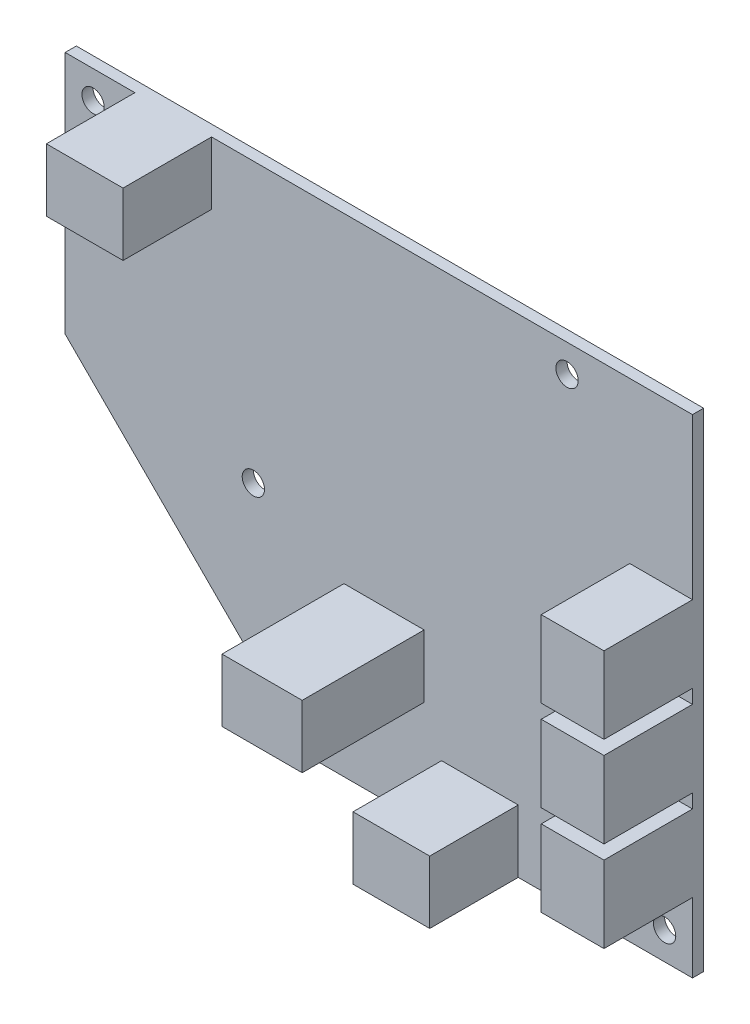
SolidWorks part; units mm, degrees
ref_plane "Plan de face" through (0, 0, 0) normal (0, 0, 1) x (1, 0, 0)
ref_plane "Plan de dessus" through (0, 0, 0) normal (0, 1, 0) x (1, 0, 0)
ref_plane "Plan de droite" through (0, 0, 0) normal (1, 0, 0) x (0, 0, -1)
sketch "Esquisse1" plane through (0, 0, 0) normal (0, 0, 1) x (1, 0, 0)
  line L0 (0, 0) -> (90, 0)
  line L1 (90, 0) -> (90, -70)
  line L2 (90, -70) -> (35, -70)
  line L3 (35, -70) -> (0, -35)
  line L4 (0, -35) -> (0, 0)
  circle A0 centre (4, -4) radius 1.6
  circle A1 centre (72, -4) radius 1.6
  circle A2 centre (27, -40) radius 1.6
  circle A3 centre (86, -66) radius 1.6
  dimension "D5" = 3.2
  dimension "D1" = 35
  dimension "D2" = 35
  dimension "D3" = 35
  dimension "D4" = 90
  dimension "D6" = 4
  dimension "D7" = 4
  dimension "D8" = 4
  dimension "D9" = 4
  dimension "D10" = 27
  dimension "D11" = 40
  dimension "D12" = 4
  dimension "D13" = 72
extrude "Boss.-Extru.1" add sketch "Esquisse1" along normal blind 1.6
sketch "Esquisse2" plane through (0, 0, 1.6) normal (0, 0, 1) x (1, 0, 0)
  line L0 (90, 0) -> (0, 0) construction
  line L1 (10, 0) -> (21, 0)
  line L2 (10, 0) -> (10, -9)
  line L3 (10, -9) -> (21, -9)
  line L4 (21, 0) -> (21, -9)
  line L5 (35, -70) -> (90, -70) construction
  line L6 (54, -70) -> (65, -70)
  line L7 (54, -70) -> (54, -61)
  line L8 (54, -61) -> (65, -61)
  line L9 (65, -70) -> (65, -61)
  line L10 (90, -70) -> (90, 0) construction
  line L11 (90, -60) -> (81, -60)
  line L12 (90, -60) -> (90, -49)
  line L13 (90, -49) -> (81, -49)
  line L14 (81, -60) -> (81, -49)
  line L15 (0, 0) -> (0, -35) construction
  line L16 (90, -47) -> (81, -47)
  line L17 (90, -47) -> (90, -36)
  line L18 (90, -36) -> (81, -36)
  line L19 (81, -47) -> (81, -36)
  line L20 (90, -34) -> (81, -34)
  line L21 (90, -34) -> (90, -23)
  line L22 (90, -23) -> (81, -23)
  line L23 (81, -34) -> (81, -23)
  dimension "D1" = 9
  dimension "D2" = 11
  dimension "D3" = 10
  dimension "D4" = 25
  dimension "D5" = 10
  dimension "D6" = 2
  dimension "D7" = 2
extrude "Boss.-Extru.2" add sketch "Esquisse2" along normal blind 12.7
sketch "Esquisse3" plane through (0, 0, 1.6) normal (0, 0, 1) x (1, 0, 0)
  line L0 (35, -70) -> (54, -70) construction
  line L1 (40, -46) -> (51.5, -46)
  line L2 (40, -46) -> (40, -55)
  line L3 (40, -55) -> (51.5, -55)
  line L4 (51.5, -46) -> (51.5, -55)
  dimension "D1" = 9
  dimension "D2" = 11.5
  dimension "D3" = 15
  dimension "D4" = 5
extrude "Boss.-Extru.3" add sketch "Esquisse3" along normal blind 17.5
